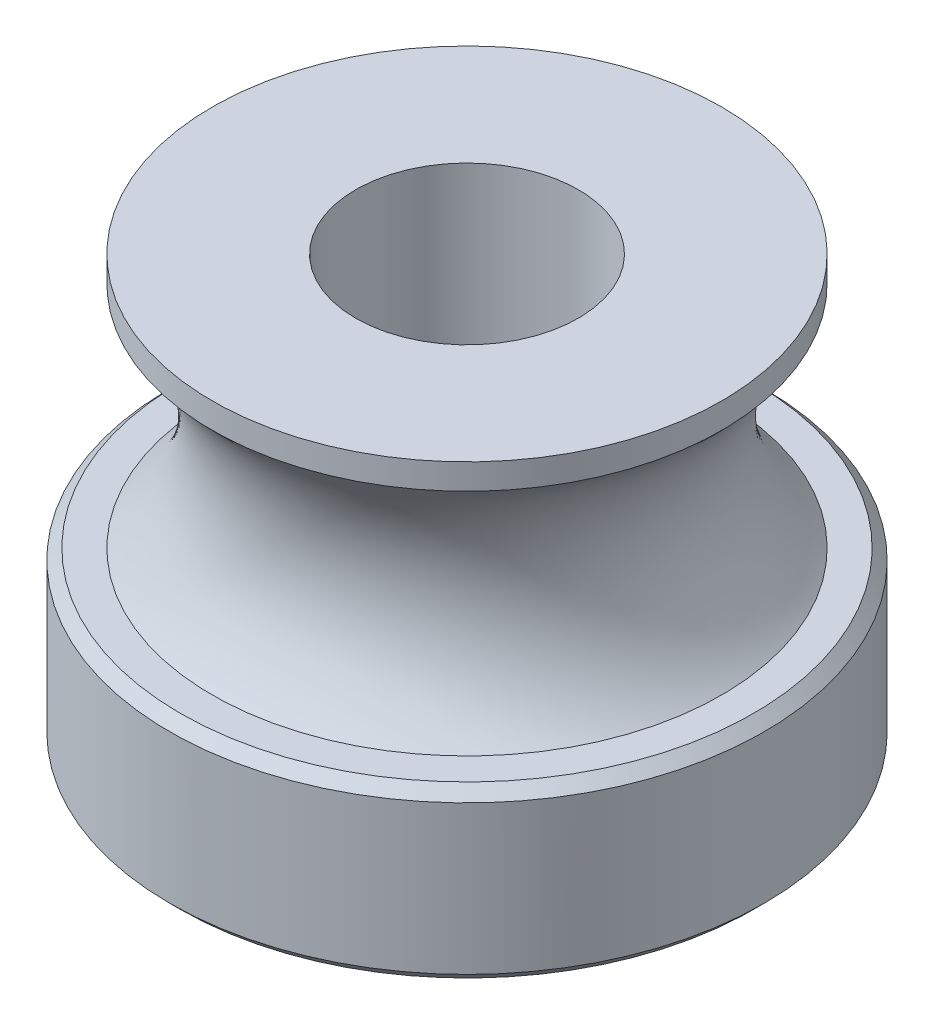
SolidWorks part; units mm, degrees
material "Brass"
ref_plane "Front Plane" through (0, 0, 0) normal (0, 0, 1) x (1, 0, 0)
ref_plane "Top Plane" through (0, 0, 0) normal (0, 1, 0) x (1, 0, 0)
ref_plane "Right Plane" through (0, 0, 0) normal (1, 0, 0) x (0, 0, -1)
sketch "Sketch1" plane through (0, 0, 0) normal (0, 0, 1) x (1, 0, 0)
  line L0 (0, 0) -> (0, 7.9375) construction
  line L1 (0, 7.9375) -> (-4.7625, 7.9375)
  line L2 (-5.5562, 3.175) -> (-5.5562, 0)
  line L3 (-5.5562, 0) -> (0, 0)
  line L4 (0, 0) -> (0, 7.9375)
  line L5 (0, 0) -> (0, -2.6189) construction
  line L6 (-3.81, 3.175) -> (-3.81, 7.9375) construction
  line L7 (-5.5562, 3.175) -> (-4.7625, 3.175)
  line L10 (-4.7625, 7.9375) -> (-4.7625, 7.4612)
  arc A0 (-4.7625, 3.175) -> (-4.7625, 7.4612) centre (-6.6973, 5.3181) ccw
  point P1 (0, 3.9688)
  dimension "D1" = 0.4763
  dimension "D2" = 0.9525
revolve "Revolve1" add sketch "Sketch1" angle 360 about L0
sketch "Sketch3" plane through (0, 0, 0) normal (0, 1, 0) x (1, 0, 0)
  circle A0 centre (0, 0) radius 2.0828
extrude "Cut-Extrude1" cut sketch "Sketch3" along normal through all
sketch "Sketch4" plane through (0, 0, 0) normal (0, 1, 0) x (1, 0, 0)
  circle A1 centre (0, 0) radius 2.0828
  circle A2 centre (0, 0) radius 2.0828
  dimension "D1" = 0
curve "Helix/Spiral1" pitch 0.7937 height 14.2875 turns 18 parameters "pitch"=0.7937
sketch "Sketch21" plane through (0, 0, 0) normal (0, 1, 0) x (1, 0, 0)
  line L0 (0, 2.0828) -> (0, 5.5562)
  circle A0 centre (0, 0) radius 5.5562 construction
  circle A1 centre (0, 0) radius 2.0828 construction
  circle A2 centre (0, 0) radius 5.5562 construction
  circle A3 centre (0, 0) radius 2.0828 construction
  dimension "D1" = 3.4734
sketch "Sketch5" plane through (0, 0, 0) normal (1, 0, 0) x (0, 0, -1)
  line L0 (-2.0828, 0) -> (-2.0828, -0.6945)
  line L1 (-2.0828, -0.6945) -> (-1.5672, -0.3969)
  line L2 (-1.5672, -0.3969) -> (-1.5672, -0.2977)
  line L3 (-1.5672, -0.2977) -> (-2.0828, 0)
  line L4 (-1.5672, -0.3473) -> (-2.0828, -0.3473) construction
  line L5 (-1.825, -0.5457) -> (-1.825, -0.1488) construction
  line L6 (2.0828, 0) -> (-2.0828, 0) construction
  dimension "D1" = 0.0992
  dimension "D2" = 0.3969
  dimension "D3" = 60
sweep "Sweep1" [suppressed] add profiles "Sketch5" path "Helix/Spiral1"
sketch "Sketch13" plane through (0, 0, 0) normal (0, -1, 0) x (1, 0, 0)
  circle A1 centre (0, 0) radius 5.5562
  circle A2 centre (0, 0) radius 5.5562
  dimension "D1" = 0
extrude "Cut-Extrude2" [suppressed] cut sketch "Sketch13" along normal through all
sketch "Sketch14" plane through (0, 7.9375, 0) normal (0, 1, 0) x (1, 0, 0)
  circle A0 centre (0, 0) radius 5.5562 construction
  circle A1 centre (0, 0) radius 5.5562
extrude "Cut-Extrude3" [suppressed] cut sketch "Sketch14" along normal through all
sketch "Sketch15" plane through (0, 0, 0) normal (0, -1, 0) x (1, 0, 0)
  circle A0 centre (0, 0) radius 2.0828 construction
  circle A1 centre (0, 0) radius 2.0828
extrude "Cut-Extrude4" [suppressed] cut sketch "Sketch15" against normal through all draft 45
sketch "Sketch16" plane through (0, 7.9375, 0) normal (0, 1, 0) x (1, 0, 0)
  circle A0 centre (0, 0) radius 2.0828 construction
  circle A1 centre (0, 0) radius 2.0828
extrude "Cut-Extrude5" [suppressed] cut sketch "Sketch16" against normal through all draft 45
chamfer "Chamfer1" distance 0.1984 angle 45 2 edges at (0, 3.175, -5.5562) (0, 0, -5.5562)
sketch "Sketch11" [suppressed] plane through (0, 0, 0) normal (0, 0, 1) x (1, 0, 0)
  line L0 (-2.0828, 7.9375) -> (-2.0828, 0)
  line L1 (2.0828, 7.9375) -> (2.0828, 0)
  line L2 (4.7625, 7.9375) -> (-4.7625, 7.9375) construction
  line L4 (-2.0828, 0) -> (2.0828, 0) construction
  dimension "D1" = 4.1656
sketch "Sketch12" plane through (0, 0, 0) normal (1, 0, 0) x (0, 0, -1)
  line L0 (-2.0828, 7.9375) -> (-2.0828, 0)
  line L1 (2.0828, 7.9375) -> (2.0828, 0)
  line L2 (-2.0828, 0) -> (2.0828, 0) construction
  line L3 (4.7625, 7.9375) -> (-4.7625, 7.9375) construction
  line L5 (-5.3578, 0) -> (5.3578, 0) construction
  dimension "D1" = 4.1656
ref_plane "Plane1" through (0, 0, -12.7) normal (0, 0, 1) x (1, 0, 0)
sketch "Sketch17" [suppressed] plane through (0, 0, -12.7) normal (0, 0, 1) x (1, 0, 0)
  line L0 (-0.127, 0.1984) -> (-0.127, 2.9766)
  line L1 (5.5562, 0.1984) -> (-5.5562, 0.1984) construction
  line L2 (5.5562, 2.9766) -> (-5.5562, 2.9766) construction
  line L3 (0.127, 0.1984) -> (0.127, 2.9766)
  line L4 (0, 0.1984) -> (0, 2.9766) construction
  line L5 (-0.127, 0.1984) -> (0.127, 0.1984)
  line L6 (-0.127, 2.9766) -> (0.127, 2.9766)
  line L7 (0, 1.5875) -> (6.048, 1.5875) construction
  line L8 (0, 1.5875) -> (0, 0) construction
  dimension "D1" = 0
  dimension "D2" = 0.254
extrude "Cut-Extrude6" [suppressed] cut sketch "Sketch17" along normal offset from surface (7.2722 mm away) 0.127 offset beyond the face yes
pattern_circular "CirPattern1" [suppressed] count 72 over 360 of bodies 116
sketch "Sketch18" [suppressed] plane through (0, 7.9375, 0) normal (0, 1, 0) x (1, 0, 0)
  circle A0 centre (0, 0) radius 5.5562
  arc A2 (1.5604, 5.3327) -> (1.315, 5.3984) centre (0, 0) ccw construction
ref_plane "Plane3" through (0, 3.9688, 0) normal (0, 1, 0) x (-1, 0, 0)
equation "\"D1@Sketch5\" = \"pitch@Helix/Spiral1\"*.125"
equation "\"D2@Sketch5\" = \"pitch@Helix/Spiral1\"*.5"
equation "\"D1@Sketch11\" = \"OD@Sketch3\""
equation "\"D1@Sketch12\" = \"OD@Sketch3\""
equation "\"D1@Chamfer1\" = \"pitch@Helix/Spiral1\"*.25"
equation "\"D3@Helix/Spiral1\" = \"B@Sketch1\"+.250"
equation "\"D1@Sketch1\" = \"D@Sketch1\"/10"
equation "\"D2@Sketch1\" = \"C@Sketch1\"*.1"
